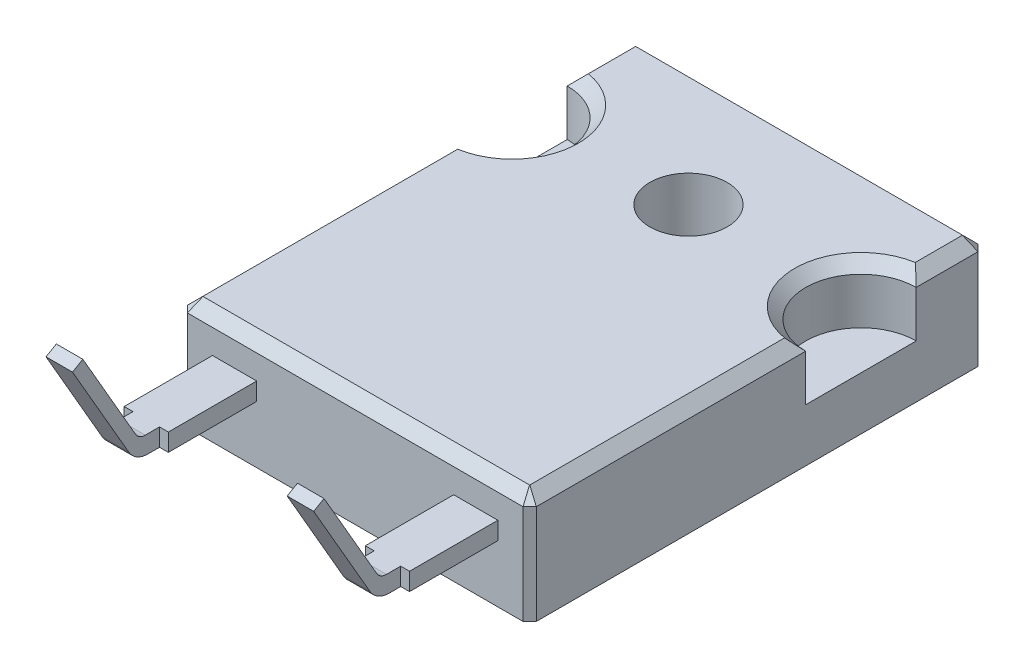
SolidWorks part; units mm, degrees
ref_plane "Спереди" through (0, 0, 0) normal (0, 0, 1) x (1, 0, 0)
ref_plane "Сверху" through (0, 0, 0) normal (0, 1, 0) x (1, 0, 0)
ref_plane "Справа" through (0, 0, 0) normal (1, 0, 0) x (0, 0, -1)
sketch "Эскиз1" plane through (0, 0, 0) normal (0, 1, 0) x (1, 0, 0)
  line L0 (0, 4.79) -> (0, -49995.21) construction
  line L1 (7.9, -10.3) -> (-7.9, -10.3)
  line L2 (7.9, -10.3) -> (7.9, 10.3)
  line L3 (7.9, 10.3) -> (-7.9, 10.3)
  line L4 (-7.9, -10.3) -> (-7.9, 10.3)
  line L5 (7.9, -10.3) -> (-7.9, 10.3) construction
  line L6 (7.9, 10.3) -> (-7.9, -10.3) construction
  line L7 (-5.46, 4.79) -> (-5.46, -49995.21) construction
  line L8 (5.46, 4.79) -> (5.46, -49995.21) construction
  line L9 (-6.46, 4.79) -> (-6.46, -49995.21) construction
  line L10 (-4.46, 4.79) -> (-4.46, -49995.21) construction
  line L11 (6.46, -10.3) -> (6.46, -14.3)
  line L12 (-6.46, -10.3) -> (-4.46, -10.3)
  line L13 (-6.46, -10.3) -> (-6.46, -14.3)
  line L14 (-6.46, -14.3) -> (-4.46, -14.3)
  line L15 (-4.46, -10.3) -> (-4.46, -14.3)
  line L16 (-6.46, -10.3) -> (-4.46, -14.3) construction
  line L17 (-6.46, -14.3) -> (-4.46, -10.3) construction
  line L18 (6.46, -14.3) -> (4.46, -14.3)
  line L19 (4.46, -10.3) -> (4.46, -14.3)
  line L20 (-6.06, 4.79) -> (-6.06, -49995.21) construction
  line L21 (-4.86, 4.79) -> (-4.86, -49995.21) construction
  line L22 (4.86, -14.3) -> (4.86, -15.4)
  line L23 (-6.06, -14.3) -> (-4.86, -14.3)
  line L24 (-6.06, -14.3) -> (-6.06, -15.4)
  line L25 (-6.06, -15.4) -> (-4.86, -15.4)
  line L26 (-4.86, -14.3) -> (-4.86, -15.4)
  line L27 (-6.06, -14.3) -> (-4.86, -15.4) construction
  line L28 (-6.06, -15.4) -> (-4.86, -14.3) construction
  line L29 (6.06, -15.4) -> (4.86, -15.4)
  line L30 (6.06, -14.3) -> (6.06, -15.4)
  line L31 (-6.06, -14.6) -> (-4.86, -14.6)
  line L32 (6.06, -14.6) -> (4.86, -14.6)
  circle A0 centre (0, 4.79) radius 1.75
  arc A1 (-7.9, 2.2) -> (-7.9, 7.2) centre (-7.9, 4.7) ccw
  arc A2 (7.9, 2.2) -> (7.9, 7.2) centre (7.9, 4.7) cw
  point P0 (0, 0)
  point P25 (-5.46, -12.3)
  point P38 (-5.46, -14.85)
  dimension "D3" = 3.5
  dimension "D6" = 5.6
  dimension "D7" = 5
  dimension "D1" = 15.8
  dimension "D2" = 20.6
  dimension "D4" = 7.9
  dimension "D5" = 5.51
  dimension "D8" = 5.46
  dimension "D9" = 5.46
  dimension "D12" = 4
  dimension "D15" = 1.1
  dimension "D16" = 0.8
  dimension "D10" = 1
  dimension "D11" = 1
  dimension "D13" = 0.6
  dimension "D14" = 0.6
extrude "Бобышка-Вытянуть1" add sketch "Эскиз1" along normal blind 2.6 contours L2 A2 L3 L4 A1 L1 A0 region at (0, 0, 0.4671)
extrude "Бобышка-Вытянуть2" add sketch "Эскиз1<3>" against normal blind 2.4 contours L2 A2 L3 L4 A1 L1 A0 | A2 L2 | L4 A1 region at (0, 0, 0.4671) region at (6.839, 0, -4.7) region at (-6.839, 0, -4.7)
sketch "Эскиз1<3>" plane through (0, 0, 0) normal (0, 1, 0) x (1, 0, 0) same geometry as "Эскиз1"
extrude "Бобышка-Вытянуть3" add sketch "Эскиз1<4>" along normal blind 0.8 from offset 0.2 separate body contours L15 L1 L13 L14 | L24 L31 L26 L14 | L31 L24 L25 L26 | L1 L19 L18 L11 | L32 L30 L18 L22 | L30 L32 L22 L29 region at (5.46, 0, 12.3) region at (-5.46, 0, 12.3) region at (5.46, 0, 14.45) region at (5.46, 0, 15) region at (-5.46, 0, 14.45) region at (-5.46, 0, 15)
sketch "Эскиз1<4>" plane through (0, 0, 0) normal (0, 1, 0) x (1, 0, 0) same geometry as "Эскиз1"
chamfer "Фаска1" distance 0.3 angle 45 4 edges at (-7.9, 0.1, 10.3) (-7.9, 0.1, -10.3) (7.9, 0.1, -10.3) (7.9, 0.1, 10.3)
chamfer "Фаска2" distance 0.5 angle 45 12 edges at (-5.4, 2.6, -4.7) (-7.9, 2.6, -8.6) (-7.75, 2.6, -10.15) (0, 2.6, -10.3) (7.75, 2.6, -10.15) (7.9, 2.6, -8.6) (5.4, 2.6, -4.7) (7.9, 2.6, 3.9) (7.75, 2.6, 10.15) (0, 2.6, 10.3) (-7.75, 2.6, 10.15) (-7.9, 2.6, 3.9)
sketch "Эскиз2" plane through (0, -2.4, 0) normal (0, -1, 0) x (1, 0, 0)
  line L0 (-6.9, -9.3) -> (6.9, -9.3)
  line L1 (6.9, -9.3) -> (6.9, -9.3)
  line L2 (6.9, -9.3) -> (6.9, 9.3)
  line L3 (6.9, 9.3) -> (6.9, 9.3)
  line L4 (6.9, 9.3) -> (-6.9, 9.3)
  line L5 (-6.9, 9.3) -> (-6.9, 9.3)
  line L6 (-6.9, 9.3) -> (-6.9, -9.3)
  line L7 (-6.9, -9.3) -> (-6.9, -9.3)
  line L8 (7.6, 10.3) -> (-7.6, 10.3)
  line L9 (-7.6, 10.3) -> (-7.9, 10)
  line L10 (-7.9, 10) -> (-7.9, -10)
  line L11 (-7.9, -10) -> (-7.6, -10.3)
  line L12 (-7.6, -10.3) -> (7.6, -10.3)
  line L13 (7.6, -10.3) -> (7.9, -10)
  line L14 (7.9, -10) -> (7.9, 10)
  line L15 (7.9, 10) -> (7.6, 10.3)
  line L16 (7.6, 10.3) -> (-7.6, 10.3)
  line L17 (-7.6, 10.3) -> (-7.9, 10)
  line L18 (-7.9, 10) -> (-7.9, -10)
  line L19 (-7.9, -10) -> (-7.6, -10.3)
  line L20 (-7.6, -10.3) -> (7.6, -10.3)
  line L21 (7.6, -10.3) -> (7.9, -10)
  line L22 (7.9, -10) -> (7.9, 10)
  line L23 (7.9, 10) -> (7.6, 10.3)
  circle A0 centre (0, -4.79) radius 1.75 construction
  circle A1 centre (0, -4.79) radius 1.75
  circle M9 centre (0, -4.79) radius 1.75
  dimension "D1" = 0
  dimension "D2" = 1
extrude "Вырез-Вытянуть1" cut sketch "Эскиз2" against normal blind 1.5 contours L4 L6 L0 L2 M9 region at (0, -2.4, 0.1865)
ref_plane "Плоскость1" through (0, 6.8184, 3.9366) normal (0, -0.866, -0.5) x (1, 0, 0)
sketch "Эскиз3" plane through (0, 6.8184, 3.9366) normal (0, -0.866, -0.5) x (1, 0, 0)
  line L0 (-6.06, 13.2368) -> (-4.86, 13.2368) construction
  line L1 (-6.06, 13.2368) -> (-4.86, 13.2368)
  line L2 (-4.86, 12.2842) -> (-4.86, 13.2368) construction
  line L3 (-6.06, 13.2368) -> (-4.86, 13.2368)
  line L4 (-6.06, 13.2368) -> (-6.06, 12.6968)
  line L5 (-6.06, 12.6968) -> (-4.86, 12.6968)
  line L6 (-4.86, 13.2368) -> (-4.86, 12.6968)
  line L7 (-6.06, 13.2368) -> (-4.86, 12.6968) construction
  line L8 (-6.06, 12.6968) -> (-4.86, 13.2368) construction
  line L9 (6.06, 13.2368) -> (6.06, 12.6968)
  line L10 (4.86, 12.6968) -> (6.06, 12.6968)
  line L11 (4.86, 13.2368) -> (6.06, 13.2368)
  line L12 (4.86, 13.2368) -> (4.86, 12.6968)
  point P4 (-5.46, 12.9668)
  point P7 (6.06, 13.2368)
  dimension "D1" = 0.54
  dimension "D2" = 2
extrude "Бобышка-Вытянуть6" add sketch "Эскиз3" against normal blind 5.68 contours L6 L1 L4 L5 | L11 L12 L10 L9 region at (-5.46, 0.335, 15.1662) region at (5.46, 0.335, 15.1662)
fillet "Скругление1" radius 1 1 edges at (-5.46, 0.2, 15.4)
fillet "Скругление2" radius 1 1 edges at (5.46, 0.2, 15.4)
fillet "Скругление3" radius 0.5 1 edges at (5.46, 1, 15.2383)
fillet "Скругление4" radius 0.5 1 edges at (-5.46, 1, 15.2383)
ref_plane "Плоскость2" through (0, -6.6184, 11.4634) normal (0, -0.5, 0.866) x (1, 0, 0)
